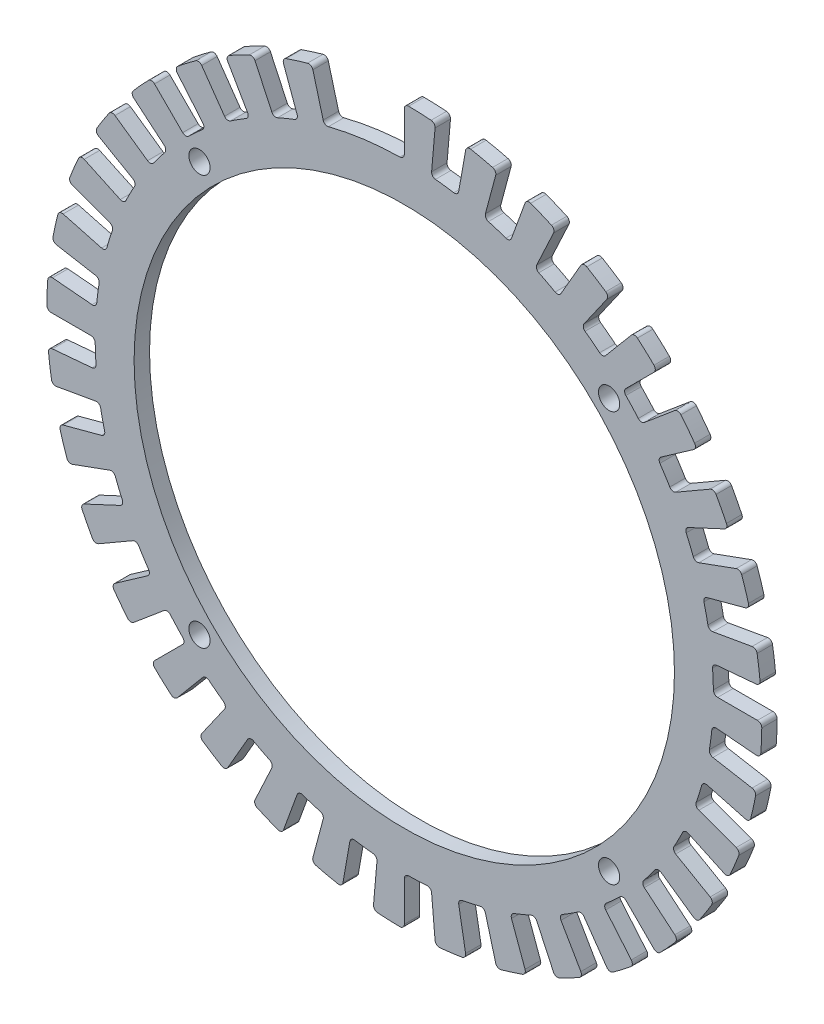
SolidWorks part; units mm, degrees
ref_plane "Front Plane" through (0, 0, 0) normal (0, 0, 1) x (1, 0, 0)
ref_plane "Top Plane" through (0, 0, 0) normal (0, 1, 0) x (1, 0, 0)
ref_plane "Right Plane" through (0, 0, 0) normal (1, 0, 0) x (0, 0, -1)
sketch "Sketch1" plane through (0, 0, 0) normal (0, 0, 1) x (1, 0, 0)
  line L0 (0, 82.7) -> (0, 71.5) construction
  line L1 (7.2078, 82.3853) -> (6.2316, 71.2279) construction
  line L2 (0, 71.5) -> (0, 0) construction
  line L3 (6.2316, 71.2279) -> (0, 0) construction
  line L4 (12.5883, 71.3918) -> (14.186, 80.4528) construction
  line L5 (12.5883, 71.3918) -> (0, 0) construction
  line L8 (0, 0) -> (47.3762, 47.3762) construction
  line L12 (50.5581, 50.5581) -> (47.3762, 47.3762) construction
  line L15 (47.3762, 47.3762) -> (44.1942, 44.1942) construction
  line L18 (7.3144, 72.1301) -> (6.3182, 72.2172) construction
  line L21 (7.3144, 72.1301) -> (7.2135, 71.1352) construction
  line L24 (12.5883, 71.3918) -> (11.6035, 71.5654) construction
  line L27 (11.6035, 71.5654) -> (11.4434, 70.5783) construction
  line L30 (1.0122, 82.6938) -> (1, 81.6939) construction
  line L33 (1, 81.6939) -> (0, 81.6939) construction
  line L36 (7.1201, 81.383) -> (6.1239, 81.4702) construction
  line L39 (6.1239, 81.4702) -> (6.1989, 82.4674) construction
  line L42 (7.1201, 81.383) -> (6.3182, 72.2172)
  line L45 (0, 81.6939) -> (0, 72.4931)
  line L48 (0, 72.4931) -> (-1, 72.4931) construction
  line L51 (-1, 72.4931) -> (-0.9862, 71.4932) construction
  line L109 (0, -82.7) -> (0, -71.5) [skipped]
  line L111 (14.3607, 81.4436) -> (12.4158, 70.4138) [skipped]
  line L115 (41.35, 71.6203) -> (35.75, 61.9208) [skipped]
  line L117 (53.1585, 63.3519) -> (45.9593, 54.7722) [skipped]
  line L118 (-63.3519, -53.1585) -> (-54.7722, -45.9593) [skipped]
  line L119 (63.3519, 53.1585) -> (54.7722, 45.9593) [skipped]
  line L121 (71.6203, 41.35) -> (61.9208, 35.75) [skipped]
  line L123 (77.7126, 28.2851) -> (67.188, 24.4544) [skipped]
  line L125 (81.4436, 14.3607) -> (70.4138, 12.4158) [skipped]
  line L127 (82.7, 0) -> (71.5, 0) [skipped]
  line L129 (81.4436, -14.3607) -> (70.4138, -12.4158) [skipped]
  line L131 (77.7126, -28.2851) -> (67.188, -24.4544) [skipped]
  line L133 (71.6203, -41.35) -> (61.9208, -35.75) [skipped]
  line L135 (63.3519, -53.1585) -> (54.7722, -45.9593) [skipped]
  line L137 (53.1585, -63.3519) -> (45.9593, -54.7722) [skipped]
  line L139 (41.35, -71.6203) -> (35.75, -61.9208) [skipped]
  line L141 (28.2851, -77.7126) -> (24.4544, -67.188) [skipped]
  line L142 (14.3607, -81.4436) -> (12.4158, -70.4138) [skipped]
  line L143 (34.9505, 74.9517) -> (30.2172, 64.801) [skipped]
  line L144 (47.4348, 67.7439) -> (41.0107, 58.5694) [skipped]
  line L145 (58.4777, 58.4777) -> (50.5581, 50.5581) [skipped]
  line L146 (67.7439, 47.4348) -> (58.5694, 41.0107) [skipped]
  line L147 (74.9517, 34.9505) -> (64.801, 30.2172) [skipped]
  line L148 (79.8821, 21.4043) -> (69.0637, 18.5056) [skipped]
  line L149 (82.3853, 7.2078) -> (71.2279, 6.2316) [skipped]
  line L150 (82.3853, -7.2078) -> (71.2279, -6.2316) [skipped]
  line L151 (79.8821, -21.4043) -> (69.0637, -18.5056) [skipped]
  line L152 (74.9517, -34.9505) -> (64.801, -30.2172) [skipped]
  line L153 (67.7439, -47.4348) -> (58.5694, -41.0107) [skipped]
  line L154 (58.4777, -58.4777) -> (50.5581, -50.5581) [skipped]
  line L155 (47.4348, -67.7439) -> (41.0107, -58.5694) [skipped]
  line L156 (34.9505, -74.9517) -> (30.2172, -64.801) [skipped]
  line L157 (21.4043, -79.8821) -> (18.5056, -69.0637) [skipped]
  line L158 (7.2078, -82.3853) -> (6.2316, -71.2279) [skipped]
  line L159 (-7.2078, -82.3853) -> (-6.2316, -71.2279) [skipped]
  line L160 (-21.4043, -79.8821) -> (-18.5056, -69.0637) [skipped]
  line L161 (-34.9505, -74.9517) -> (-30.2172, -64.801) [skipped]
  line L162 (-47.4348, -67.7439) -> (-41.0107, -58.5694) [skipped]
  line L163 (-58.4777, -58.4777) -> (-50.5581, -50.5581) [skipped]
  line L164 (-67.7439, -47.4348) -> (-58.5694, -41.0107) [skipped]
  line L165 (-74.9517, -34.9505) -> (-64.801, -30.2172) [skipped]
  line L166 (-79.8821, -21.4043) -> (-69.0637, -18.5056) [skipped]
  line L167 (-82.3853, -7.2078) -> (-71.2279, -6.2316) [skipped]
  line L168 (-82.3853, 7.2078) -> (-71.2279, 6.2316) [skipped]
  line L169 (-79.8821, 21.4043) -> (-69.0637, 18.5056) [skipped]
  line L170 (-74.9517, 34.9505) -> (-64.801, 30.2172) [skipped]
  line L171 (-67.7439, 47.4348) -> (-58.5694, 41.0107) [skipped]
  line L172 (-58.4777, 58.4777) -> (-50.5581, 50.5581) [skipped]
  line L173 (-47.4348, 67.7439) -> (-41.0107, 58.5694) [skipped]
  line L174 (-34.9505, 74.9517) -> (-30.2172, 64.801) [skipped]
  line L175 (-21.4043, 79.8821) -> (-18.5056, 69.0637) [skipped]
  line L176 (21.4043, 79.8821) -> (18.5056, 69.0637) [skipped]
  line L209 (0, 0) -> (-47.3762, -47.3762) construction
  line L210 (0, 0) -> (-47.3762, 47.3762) construction
  line L211 (0, 0) -> (47.3762, -47.3762) construction
  line L212 (14.186, 80.4528) -> (12.5883, 71.3918)
  line L213 (21.1439, 78.9102) -> (18.7626, 70.023)
  line L214 (27.941, 76.7671) -> (24.7941, 68.1212)
  line L215 (34.5253, 74.0398) -> (30.6369, 65.7011)
  line L216 (40.8469, 70.749) -> (36.2466, 62.7809)
  line L217 (46.8577, 66.9197) -> (41.5803, 59.3829)
  line L218 (52.5118, 62.5811) -> (46.5977, 55.5329)
  line L219 (57.7663, 57.7663) -> (51.2604, 51.2604)
  line L220 (62.5811, 52.5118) -> (55.5329, 46.5977)
  line L221 (66.9197, 46.8577) -> (59.3829, 41.5803)
  line L222 (70.749, 40.8469) -> (62.7809, 36.2466)
  line L223 (74.0398, 34.5253) -> (65.7011, 30.6369)
  line L224 (76.7671, 27.941) -> (68.1212, 24.7941)
  line L225 (78.9102, 21.1439) -> (70.023, 18.7626)
  line L226 (80.4528, 14.186) -> (71.3918, 12.5883)
  line L227 (81.383, 7.1201) -> (72.2172, 6.3182)
  line L228 (81.6939, 0) -> (72.4931, 0)
  line L229 (81.383, -7.1201) -> (72.2172, -6.3182)
  line L230 (80.4528, -14.186) -> (71.3918, -12.5883)
  line L231 (78.9102, -21.1439) -> (70.023, -18.7626)
  line L232 (76.7671, -27.941) -> (68.1212, -24.7941)
  line L233 (74.0398, -34.5253) -> (65.7011, -30.6369)
  line L234 (70.749, -40.8469) -> (62.7809, -36.2466)
  line L235 (66.9197, -46.8577) -> (59.3829, -41.5803)
  line L236 (62.5811, -52.5118) -> (55.5329, -46.5977)
  line L237 (57.7663, -57.7663) -> (51.2604, -51.2604)
  line L238 (52.5118, -62.5811) -> (46.5977, -55.5329)
  line L239 (46.8577, -66.9197) -> (41.5803, -59.3829)
  line L240 (40.8469, -70.749) -> (36.2466, -62.7809)
  line L241 (34.5253, -74.0398) -> (30.6369, -65.7011)
  line L242 (27.941, -76.7671) -> (24.7941, -68.1212)
  line L243 (21.1439, -78.9102) -> (18.7626, -70.023)
  line L244 (14.186, -80.4528) -> (12.5883, -71.3918)
  line L245 (7.1201, -81.383) -> (6.3182, -72.2172)
  line L246 (0, -81.6939) -> (0, -72.4931)
  line L247 (-7.1201, -81.383) -> (-6.3182, -72.2172)
  line L248 (-14.186, -80.4528) -> (-12.5883, -71.3918)
  line L249 (-21.1439, -78.9102) -> (-18.7626, -70.023)
  line L250 (-27.941, -76.7671) -> (-24.7941, -68.1212)
  line L251 (-34.5253, -74.0398) -> (-30.6369, -65.7011)
  line L252 (-40.8469, -70.749) -> (-36.2466, -62.7809)
  line L253 (-46.8577, -66.9197) -> (-41.5803, -59.3829)
  line L254 (-52.5118, -62.5811) -> (-46.5977, -55.5329)
  line L255 (-57.7663, -57.7663) -> (-51.2604, -51.2604)
  line L256 (-62.5811, -52.5118) -> (-55.5329, -46.5977)
  line L257 (-66.9197, -46.8577) -> (-59.3829, -41.5803)
  line L258 (-70.749, -40.8469) -> (-62.7809, -36.2466)
  line L259 (-74.0398, -34.5253) -> (-65.7011, -30.6369)
  line L260 (-76.7671, -27.941) -> (-68.1212, -24.7941)
  line L261 (-78.9102, -21.1439) -> (-70.023, -18.7626)
  line L262 (-80.4528, -14.186) -> (-71.3918, -12.5883)
  line L263 (-81.383, -7.1201) -> (-72.2172, -6.3182)
  line L264 (-81.6939, 0) -> (-72.4931, 0)
  line L265 (-81.383, 7.1201) -> (-72.2172, 6.3182)
  line L266 (-80.4528, 14.186) -> (-71.3918, 12.5883)
  line L267 (-78.9102, 21.1439) -> (-70.023, 18.7626)
  line L268 (-76.7671, 27.941) -> (-68.1212, 24.7941)
  line L269 (-74.0398, 34.5253) -> (-65.7011, 30.6369)
  line L270 (-70.749, 40.8469) -> (-62.7809, 36.2466)
  line L271 (-66.9197, 46.8577) -> (-59.3829, 41.5803)
  line L272 (-62.5811, 52.5118) -> (-55.5329, 46.5977)
  line L273 (-57.7663, 57.7663) -> (-51.2604, 51.2604)
  line L274 (-52.5118, 62.5811) -> (-46.5977, 55.5329)
  line L275 (-46.8577, 66.9197) -> (-41.5803, 59.3829)
  line L276 (-40.8469, 70.749) -> (-36.2466, 62.7809)
  line L277 (-34.5253, 74.0398) -> (-30.6369, 65.7011)
  line L278 (-27.941, 76.7671) -> (-24.7941, 68.1212)
  line L279 (-21.1439, 78.9102) -> (-18.7626, 70.023)
  line L280 (-1.0255, 71.4926) -> (-0.9862, 71.4932)
  circle A0 centre (0, 0) radius 82.7 construction
  circle A1 centre (0, 0) radius 62.5
  circle A73 centre (47.3762, 47.3762) radius 2.4585
  circle A74 centre (47.3762, 47.3762) radius 2.987 construction
  arc A78 (0, 71.5) -> (6.2316, 71.2279) centre (0, 0) cw construction
  arc A79 (6.3182, 72.2172) -> (7.2135, 71.1352) centre (7.3144, 72.1301) ccw
  arc A80 (11.4434, 70.5783) -> (12.5883, 71.3918) centre (11.6035, 71.5654) ccw construction
  arc A81 (7.1201, 81.383) -> (6.1989, 82.4674) centre (6.1239, 81.4702) ccw
  arc A82 (0, 81.6939) -> (1.0122, 82.6938) centre (1, 81.6939) cw
  arc A83 (6.5367, 74.7146) -> (13.0236, 73.8606) centre (0, 0) cw [skipped]
  arc A84 (7.2135, 71.1352) -> (11.4434, 70.5783) centre (0, 0) cw
  arc A85 (0, 82.7) -> (7.2078, 82.3853) centre (0, 0) cw [skipped]
  arc A86 (1.0122, 82.6938) -> (6.1989, 82.4674) centre (0, 0) cw
  arc A87 (28.2851, 77.7126) -> (34.9505, 74.9517) centre (0, 0) cw [skipped]
  arc A88 (31.6964, 67.9731) -> (37.5, 64.9519) centre (0, 0) cw [skipped]
  arc A89 (41.35, 71.6203) -> (47.4348, 67.7439) centre (0, 0) cw [skipped]
  arc A90 (43.0182, 61.4364) -> (48.2091, 57.4533) centre (0, 0) cw [skipped]
  arc A91 (53.1585, 63.3519) -> (58.4777, 58.4777) centre (0, 0) cw [skipped]
  arc A92 (53.033, 53.033) -> (57.4533, 48.2091) centre (0, 0) cw [skipped]
  arc A93 (63.3519, 53.1585) -> (67.7439, 47.4348) centre (0, 0) cw [skipped]
  arc A94 (61.4364, 43.0182) -> (64.9519, 37.5) centre (0, 0) cw [skipped]
  arc A95 (71.6203, 41.35) -> (74.9517, 34.9505) centre (0, 0) cw [skipped]
  arc A96 (67.9731, 31.6964) -> (70.4769, 25.6515) centre (0, 0) cw [skipped]
  arc A97 (77.7126, 28.2851) -> (79.8821, 21.4043) centre (0, 0) cw [skipped]
  arc A98 (72.4444, 19.4114) -> (73.8606, 13.0236) centre (0, 0) cw [skipped]
  arc A99 (81.4436, 14.3607) -> (82.3853, 7.2078) centre (0, 0) cw [skipped]
  arc A100 (74.7146, 6.5367) -> (75, 0) centre (0, 0) cw [skipped]
  arc A101 (82.7, 0) -> (82.3853, -7.2078) centre (0, 0) cw [skipped]
  arc A102 (74.7146, -6.5367) -> (73.8606, -13.0236) centre (0, 0) cw [skipped]
  arc A103 (81.4436, -14.3607) -> (79.8821, -21.4043) centre (0, 0) cw [skipped]
  arc A104 (72.4444, -19.4114) -> (70.4769, -25.6515) centre (0, 0) cw [skipped]
  arc A105 (77.7126, -28.2851) -> (74.9517, -34.9505) centre (0, 0) cw [skipped]
  arc A106 (67.9731, -31.6964) -> (64.9519, -37.5) centre (0, 0) cw [skipped]
  arc A107 (71.6203, -41.35) -> (67.7439, -47.4348) centre (0, 0) cw [skipped]
  arc A108 (61.4364, -43.0182) -> (57.4533, -48.2091) centre (0, 0) cw [skipped]
  arc A109 (63.3519, -53.1585) -> (58.4777, -58.4777) centre (0, 0) cw [skipped]
  arc A110 (53.033, -53.033) -> (48.2091, -57.4533) centre (0, 0) cw [skipped]
  arc A111 (53.1585, -63.3519) -> (47.4348, -67.7439) centre (0, 0) cw [skipped]
  arc A112 (43.0182, -61.4364) -> (37.5, -64.9519) centre (0, 0) cw [skipped]
  arc A113 (41.35, -71.6203) -> (34.9505, -74.9517) centre (0, 0) cw [skipped]
  arc A114 (31.6964, -67.9731) -> (25.6515, -70.4769) centre (0, 0) cw [skipped]
  arc A115 (28.2851, -77.7126) -> (21.4043, -79.8821) centre (0, 0) cw [skipped]
  arc A116 (19.4114, -72.4444) -> (13.0236, -73.8606) centre (0, 0) cw [skipped]
  arc A117 (14.3607, -81.4436) -> (7.2078, -82.3853) centre (0, 0) cw [skipped]
  arc A118 (6.5367, -74.7146) -> (0, -75) centre (0, 0) cw [skipped]
  arc A119 (0, -82.7) -> (-7.2078, -82.3853) centre (0, 0) cw [skipped]
  arc A120 (-6.5367, -74.7146) -> (-13.0236, -73.8606) centre (0, 0) cw [skipped]
  arc A121 (-14.3607, -81.4436) -> (-21.4043, -79.8821) centre (0, 0) cw [skipped]
  arc A122 (-28.2851, -77.7126) -> (-34.9505, -74.9517) centre (0, 0) cw [skipped]
  arc A123 (-19.4114, -72.4444) -> (-25.6515, -70.4769) centre (0, 0) cw [skipped]
  arc A124 (-31.6964, -67.9731) -> (-37.5, -64.9519) centre (0, 0) cw [skipped]
  arc A125 (-41.35, -71.6203) -> (-47.4348, -67.7439) centre (0, 0) cw [skipped]
  arc A126 (-43.0182, -61.4364) -> (-48.2091, -57.4533) centre (0, 0) cw [skipped]
  arc A127 (-53.1585, -63.3519) -> (-58.4777, -58.4777) centre (0, 0) cw [skipped]
  arc A128 (-53.033, -53.033) -> (-57.4533, -48.2091) centre (0, 0) cw [skipped]
  arc A129 (-63.3519, -53.1585) -> (-67.7439, -47.4348) centre (0, 0) cw [skipped]
  arc A130 (-61.4364, -43.0182) -> (-64.9519, -37.5) centre (0, 0) cw [skipped]
  arc A131 (-71.6203, -41.35) -> (-74.9517, -34.9505) centre (0, 0) cw [skipped]
  arc A132 (-67.9731, -31.6964) -> (-70.4769, -25.6515) centre (0, 0) cw [skipped]
  arc A133 (-77.7126, -28.2851) -> (-79.8821, -21.4043) centre (0, 0) cw [skipped]
  arc A134 (-72.4444, -19.4114) -> (-73.8606, -13.0236) centre (0, 0) cw [skipped]
  arc A135 (-81.4436, -14.3607) -> (-82.3853, -7.2078) centre (0, 0) cw [skipped]
  arc A136 (-74.7146, -6.5367) -> (-75, 0) centre (0, 0) cw [skipped]
  arc A137 (-82.7, 0) -> (-82.3853, 7.2078) centre (0, 0) cw [skipped]
  arc A138 (-74.7146, 6.5367) -> (-73.8606, 13.0236) centre (0, 0) cw [skipped]
  arc A139 (-81.4436, 14.3607) -> (-79.8821, 21.4043) centre (0, 0) cw [skipped]
  arc A140 (-72.4444, 19.4114) -> (-70.4769, 25.6515) centre (0, 0) cw [skipped]
  arc A141 (-77.7126, 28.2851) -> (-74.9517, 34.9505) centre (0, 0) cw [skipped]
  arc A142 (-67.9731, 31.6964) -> (-64.9519, 37.5) centre (0, 0) cw [skipped]
  arc A143 (-71.6203, 41.35) -> (-67.7439, 47.4348) centre (0, 0) cw [skipped]
  arc A144 (-61.4364, 43.0182) -> (-57.4533, 48.2091) centre (0, 0) cw [skipped]
  arc A145 (-63.3519, 53.1585) -> (-58.4777, 58.4777) centre (0, 0) cw [skipped]
  arc A146 (-53.033, 53.033) -> (-48.2091, 57.4533) centre (0, 0) cw [skipped]
  arc A147 (-53.1585, 63.3519) -> (-47.4348, 67.7439) centre (0, 0) cw [skipped]
  arc A148 (-43.0182, 61.4364) -> (-37.5, 64.9519) centre (0, 0) cw [skipped]
  arc A149 (-41.35, 71.6203) -> (-34.9505, 74.9517) centre (0, 0) cw [skipped]
  arc A150 (-31.6964, 67.9731) -> (-25.6515, 70.4769) centre (0, 0) cw [skipped]
  arc A151 (-28.2851, 77.7126) -> (-21.4043, 79.8821) centre (0, 0) cw [skipped]
  arc A152 (-19.4114, 72.4444) -> (-13.0236, 73.8606) centre (0, 0) cw [skipped]
  arc A153 (14.3607, 81.4436) -> (21.4043, 79.8821) centre (0, 0) cw [skipped]
  arc A154 (19.4114, 72.4444) -> (25.6515, 70.4769) centre (0, 0) cw [skipped]
  arc A155 (0, 72.4931) -> (-0.9862, 71.4932) centre (-1, 72.4931) cw
  circle A367 centre (-47.3762, -47.3762) radius 2.4585
  circle A368 centre (47.3762, -47.3762) radius 2.4585
  circle A369 centre (-47.3762, 47.3762) radius 2.4585
  circle A370 centre (0, 0) radius 71.5 construction
  arc A371 (12.5883, 71.3918) -> (11.4434, 70.5783) centre (11.6035, 71.5654) cw
  arc A372 (14.186, 80.4528) -> (15.3565, 81.2617) centre (15.1708, 80.2791) cw
  arc A373 (15.3565, 81.2617) -> (20.425, 80.1381) centre (0, 0) cw
  arc A374 (21.1439, 78.9102) -> (20.425, 80.1381) centre (20.178, 79.169) ccw
  arc A375 (18.7626, 70.023) -> (19.4564, 68.8019) centre (19.7285, 69.7641) ccw
  arc A376 (19.4564, 68.8019) -> (23.5254, 67.5189) centre (0, 0) cw
  arc A377 (24.7941, 68.1212) -> (23.5254, 67.5189) centre (23.8544, 68.4633) cw
  arc A378 (27.941, 76.7671) -> (29.2341, 77.3606) centre (28.8806, 76.4251) cw
  arc A379 (29.2341, 77.3606) -> (34.0305, 75.3738) centre (0, 0) cw
  arc A380 (34.5253, 74.0398) -> (34.0305, 75.3738) centre (33.619, 74.4624) ccw
  arc A381 (30.6369, 65.7011) -> (31.1081, 64.3781) centre (31.5432, 65.2784) ccw
  arc A382 (31.1081, 64.3781) -> (34.8925, 62.408) centre (0, 0) cw
  arc A384 (36.2466, 62.7809) -> (34.8925, 62.408) centre (35.3805, 63.2809) cw
  arc A385 (40.8469, 70.749) -> (42.2235, 71.1088) centre (41.713, 70.249) cw
  arc A386 (42.2235, 71.1088) -> (46.602, 68.3194) centre (0, 0) cw
  arc A387 (46.8577, 66.9197) -> (46.602, 68.3194) centre (46.0385, 67.4933) ccw
  arc A388 (41.5803, 59.3829) -> (41.8147, 57.9981) centre (42.3995, 58.8093) ccw
  arc A389 (41.8147, 57.9981) -> (45.1995, 55.4009) centre (0, 0) cw
  arc A390 (46.5977, 55.5329) -> (45.1995, 55.4009) centre (45.8316, 56.1757) cw
  arc A391 (52.5118, 62.5811) -> (53.93, 62.6965) centre (53.2779, 61.9384) cw
  arc A392 (53.93, 62.6965) -> (57.7576, 59.1891) centre (0, 0) cw
  arc A393 (57.7663, 57.7663) -> (57.7576, 59.1891) centre (57.0592, 58.4734) ccw
  arc A394 (51.2604, 51.2604) -> (51.2507, 49.856) centre (51.9675, 50.5533) ccw
  arc A395 (51.2507, 49.856) -> (54.133, 46.7104) centre (0, 0) cw
  arc A396 (55.5329, 46.5977) -> (54.133, 46.7104) centre (54.8902, 47.3637) cw
  arc A397 (62.5811, 52.5118) -> (63.9978, 52.3791) centre (63.2239, 51.7458) cw
  arc A398 (63.9978, 52.3791) -> (67.1582, 48.2604) centre (0, 0) cw
  arc A399 (66.9197, 46.8577) -> (67.1582, 48.2604) centre (66.3461, 47.6768) ccw
  arc A400 (59.3829, 41.5803) -> (59.1295, 40.199) centre (59.9565, 40.7612) ccw
  arc A401 (59.1295, 40.199) -> (61.4218, 36.6007) centre (0, 0) cw
  arc A402 (62.7809, 36.2466) -> (61.4218, 36.6007) centre (62.2809, 37.1126) cw
  arc A403 (70.749, 40.8469) -> (72.1211, 40.4703) centre (71.249, 39.9809) cw
  arc A404 (72.1211, 40.4703) -> (74.5182, 35.8653) centre (0, 0) cw
  arc A405 (74.0398, 34.5253) -> (74.5182, 35.8653) centre (73.6172, 35.4316) ccw
  arc A406 (65.7011, 30.6369) -> (65.2116, 29.3205) centre (66.1237, 29.7306) ccw
  arc A407 (65.2116, 29.3205) -> (66.8443, 25.3788) centre (0, 0) cw
  arc A408 (68.1212, 24.7941) -> (66.8443, 25.3788) centre (67.7792, 25.7338) cw
  arc A409 (76.7671, 27.941) -> (78.053, 27.3318) centre (77.1092, 27.0013) cw
  arc A410 (78.053, 27.3318) -> (79.6141, 22.3805) centre (0, 0) cw
  arc A411 (78.9102, 21.1439) -> (79.6141, 22.3805) centre (78.6514, 22.1099) ccw
  arc A412 (70.023, 18.7626) -> (69.3124, 17.5512) centre (70.2818, 17.7967) ccw
  arc A413 (69.3124, 17.5512) -> (70.2358, 13.3859) centre (0, 0) cw
  arc A414 (71.3918, 12.5883) -> (70.2358, 13.3859) centre (71.2181, 13.5731) cw
  arc A415 (80.4528, 14.186) -> (81.6133, 13.3628) centre (80.6264, 13.2012) cw
  arc A416 (81.6133, 13.3628) -> (82.2909, 8.2156) centre (0, 0) cw
  arc A417 (81.383, 7.1201) -> (82.2909, 8.2156) centre (81.2959, 8.1163) ccw
  arc A418 (72.2172, 6.3182) -> (71.3071, 5.2486) centre (72.3044, 5.322) ccw
  arc A419 (71.3071, 5.2486) -> (71.4932, 0.9862) centre (0, 0) cw
  arc A420 (72.4931, 0) -> (71.4932, 0.9862) centre (72.4931, 1) cw
  arc A421 (81.6939, 0) -> (82.6938, -1.0122) centre (81.6939, -1) cw
  arc A422 (82.6938, -1.0122) -> (82.4674, -6.1989) centre (0, 0) cw
  arc A423 (81.383, -7.1201) -> (82.4674, -6.1989) centre (81.4702, -6.1239) ccw
  arc A424 (72.2172, -6.3182) -> (71.1352, -7.2135) centre (72.1301, -7.3144) ccw
  arc A425 (71.1352, -7.2135) -> (70.5783, -11.4434) centre (0, 0) cw
  arc A426 (71.3918, -12.5883) -> (70.5783, -11.4434) centre (71.5654, -11.6035) cw
  arc A427 (80.4528, -14.186) -> (81.2617, -15.3565) centre (80.2791, -15.1708) cw
  arc A428 (81.2617, -15.3565) -> (80.1381, -20.425) centre (0, 0) cw
  arc A429 (78.9102, -21.1439) -> (80.1381, -20.425) centre (79.169, -20.178) ccw
  arc A430 (70.023, -18.7626) -> (68.8019, -19.4564) centre (69.7641, -19.7285) ccw
  arc A431 (68.8019, -19.4564) -> (67.5189, -23.5254) centre (0, 0) cw
  arc A432 (68.1212, -24.7941) -> (67.5189, -23.5254) centre (68.4633, -23.8544) cw
  arc A433 (76.7671, -27.941) -> (77.3606, -29.2341) centre (76.4251, -28.8806) cw
  arc A434 (77.3606, -29.2341) -> (75.3738, -34.0305) centre (0, 0) cw
  arc A435 (74.0398, -34.5253) -> (75.3738, -34.0305) centre (74.4624, -33.619) ccw
  arc A436 (65.7011, -30.6369) -> (64.3781, -31.1081) centre (65.2784, -31.5432) ccw
  arc A437 (64.3781, -31.1081) -> (62.408, -34.8925) centre (0, 0) cw
  arc A438 (62.7809, -36.2466) -> (62.408, -34.8925) centre (63.2809, -35.3805) cw
  arc A439 (70.749, -40.8469) -> (71.1088, -42.2235) centre (70.249, -41.713) cw
  arc A440 (71.1088, -42.2235) -> (68.3194, -46.602) centre (0, 0) cw
  arc A441 (66.9197, -46.8577) -> (68.3194, -46.602) centre (67.4933, -46.0385) ccw
  arc A442 (59.3829, -41.5803) -> (57.9981, -41.8147) centre (58.8093, -42.3995) ccw
  arc A443 (57.9981, -41.8147) -> (55.4009, -45.1995) centre (0, 0) cw
  arc A444 (55.5329, -46.5977) -> (55.4009, -45.1995) centre (56.1757, -45.8316) cw
  arc A445 (62.5811, -52.5118) -> (62.6965, -53.93) centre (61.9384, -53.2779) cw
  arc A446 (62.6965, -53.93) -> (59.1891, -57.7576) centre (0, 0) cw
  arc A447 (57.7663, -57.7663) -> (59.1891, -57.7576) centre (58.4734, -57.0592) ccw
  arc A448 (51.2604, -51.2604) -> (49.856, -51.2507) centre (50.5533, -51.9675) ccw
  arc A449 (49.856, -51.2507) -> (46.7104, -54.133) centre (0, 0) cw
  arc A450 (46.5977, -55.5329) -> (46.7104, -54.133) centre (47.3637, -54.8902) cw
  arc A451 (52.5118, -62.5811) -> (52.3791, -63.9978) centre (51.7458, -63.2239) cw
  arc A452 (52.3791, -63.9978) -> (48.2604, -67.1582) centre (0, 0) cw
  arc A453 (46.8577, -66.9197) -> (48.2604, -67.1582) centre (47.6768, -66.3461) ccw
  arc A454 (41.5803, -59.3829) -> (40.199, -59.1295) centre (40.7612, -59.9565) ccw
  arc A455 (40.199, -59.1295) -> (36.6007, -61.4218) centre (0, 0) cw
  arc A456 (36.2466, -62.7809) -> (36.6007, -61.4218) centre (37.1126, -62.2809) cw
  arc A457 (40.8469, -70.749) -> (40.4703, -72.1211) centre (39.9809, -71.249) cw
  arc A458 (40.4703, -72.1211) -> (35.8653, -74.5182) centre (0, 0) cw
  arc A459 (34.5253, -74.0398) -> (35.8653, -74.5182) centre (35.4316, -73.6172) ccw
  arc A460 (30.6369, -65.7011) -> (29.3205, -65.2116) centre (29.7306, -66.1237) ccw
  arc A461 (29.3205, -65.2116) -> (25.3788, -66.8443) centre (0, 0) cw
  arc A462 (24.7941, -68.1212) -> (25.3788, -66.8443) centre (25.7338, -67.7792) cw
  arc A463 (27.941, -76.7671) -> (27.3318, -78.053) centre (27.0013, -77.1092) cw
  arc A464 (27.3318, -78.053) -> (22.3805, -79.6141) centre (0, 0) cw
  arc A465 (21.1439, -78.9102) -> (22.3805, -79.6141) centre (22.1099, -78.6514) ccw
  arc A466 (18.7626, -70.023) -> (17.5512, -69.3124) centre (17.7967, -70.2818) ccw
  arc A467 (17.5512, -69.3124) -> (13.3859, -70.2358) centre (0, 0) cw
  arc A468 (12.5883, -71.3918) -> (13.3859, -70.2358) centre (13.5731, -71.2181) cw
  arc A469 (14.186, -80.4528) -> (13.3628, -81.6133) centre (13.2012, -80.6264) cw
  arc A470 (13.3628, -81.6133) -> (8.2156, -82.2909) centre (0, 0) cw
  arc A471 (7.1201, -81.383) -> (8.2156, -82.2909) centre (8.1163, -81.2959) ccw
  arc A472 (6.3182, -72.2172) -> (5.2486, -71.3071) centre (5.322, -72.3044) ccw
  arc A473 (5.2486, -71.3071) -> (0.9862, -71.4932) centre (0, 0) cw
  arc A474 (0, -72.4931) -> (0.9862, -71.4932) centre (1, -72.4931) cw
  arc A475 (0, -81.6939) -> (-1.0122, -82.6938) centre (-1, -81.6939) cw
  arc A476 (-1.0122, -82.6938) -> (-6.1989, -82.4674) centre (0, 0) cw
  arc A477 (-7.1201, -81.383) -> (-6.1989, -82.4674) centre (-6.1239, -81.4702) ccw
  arc A478 (-6.3182, -72.2172) -> (-7.2135, -71.1352) centre (-7.3144, -72.1301) ccw
  arc A479 (-7.2135, -71.1352) -> (-11.4434, -70.5783) centre (0, 0) cw
  arc A480 (-12.5883, -71.3918) -> (-11.4434, -70.5783) centre (-11.6035, -71.5654) cw
  arc A481 (-14.186, -80.4528) -> (-15.3565, -81.2617) centre (-15.1708, -80.2791) cw
  arc A482 (-15.3565, -81.2617) -> (-20.425, -80.1381) centre (0, 0) cw
  arc A483 (-21.1439, -78.9102) -> (-20.425, -80.1381) centre (-20.178, -79.169) ccw
  arc A484 (-18.7626, -70.023) -> (-19.4564, -68.8019) centre (-19.7285, -69.7641) ccw
  arc A485 (-19.4564, -68.8019) -> (-23.5254, -67.5189) centre (0, 0) cw
  arc A486 (-24.7941, -68.1212) -> (-23.5254, -67.5189) centre (-23.8544, -68.4633) cw
  arc A487 (-27.941, -76.7671) -> (-29.2341, -77.3606) centre (-28.8806, -76.4251) cw
  arc A488 (-29.2341, -77.3606) -> (-34.0305, -75.3738) centre (0, 0) cw
  arc A489 (-34.5253, -74.0398) -> (-34.0305, -75.3738) centre (-33.619, -74.4624) ccw
  arc A490 (-30.6369, -65.7011) -> (-31.1081, -64.3781) centre (-31.5432, -65.2784) ccw
  arc A491 (-31.1081, -64.3781) -> (-34.8925, -62.408) centre (0, 0) cw
  arc A492 (-36.2466, -62.7809) -> (-34.8925, -62.408) centre (-35.3805, -63.2809) cw
  arc A493 (-40.8469, -70.749) -> (-42.2235, -71.1088) centre (-41.713, -70.249) cw
  arc A494 (-42.2235, -71.1088) -> (-46.602, -68.3194) centre (0, 0) cw
  arc A495 (-46.8577, -66.9197) -> (-46.602, -68.3194) centre (-46.0385, -67.4933) ccw
  arc A496 (-41.5803, -59.3829) -> (-41.8147, -57.9981) centre (-42.3995, -58.8093) ccw
  arc A497 (-41.8147, -57.9981) -> (-45.1995, -55.4009) centre (0, 0) cw
  arc A498 (-46.5977, -55.5329) -> (-45.1995, -55.4009) centre (-45.8316, -56.1757) cw
  arc A499 (-52.5118, -62.5811) -> (-53.93, -62.6965) centre (-53.2779, -61.9384) cw
  arc A500 (-53.93, -62.6965) -> (-57.7576, -59.1891) centre (0, 0) cw
  arc A501 (-57.7663, -57.7663) -> (-57.7576, -59.1891) centre (-57.0592, -58.4734) ccw
  arc A502 (-51.2604, -51.2604) -> (-51.2507, -49.856) centre (-51.9675, -50.5533) ccw
  arc A503 (-51.2507, -49.856) -> (-54.133, -46.7104) centre (0, 0) cw
  arc A504 (-55.5329, -46.5977) -> (-54.133, -46.7104) centre (-54.8902, -47.3637) cw
  arc A505 (-62.5811, -52.5118) -> (-63.9978, -52.3791) centre (-63.2239, -51.7458) cw
  arc A506 (-63.9978, -52.3791) -> (-67.1582, -48.2604) centre (0, 0) cw
  arc A507 (-66.9197, -46.8577) -> (-67.1582, -48.2604) centre (-66.3461, -47.6768) ccw
  arc A508 (-59.3829, -41.5803) -> (-59.1295, -40.199) centre (-59.9565, -40.7612) ccw
  arc A509 (-59.1295, -40.199) -> (-61.4218, -36.6007) centre (0, 0) cw
  arc A510 (-62.7809, -36.2466) -> (-61.4218, -36.6007) centre (-62.2809, -37.1126) cw
  arc A511 (-70.749, -40.8469) -> (-72.1211, -40.4703) centre (-71.249, -39.9809) cw
  arc A512 (-72.1211, -40.4703) -> (-74.5182, -35.8653) centre (0, 0) cw
  arc A513 (-74.0398, -34.5253) -> (-74.5182, -35.8653) centre (-73.6172, -35.4316) ccw
  arc A514 (-65.7011, -30.6369) -> (-65.2116, -29.3205) centre (-66.1237, -29.7306) ccw
  arc A515 (-65.2116, -29.3205) -> (-66.8443, -25.3788) centre (0, 0) cw
  arc A516 (-68.1212, -24.7941) -> (-66.8443, -25.3788) centre (-67.7792, -25.7338) cw
  arc A517 (-76.7671, -27.941) -> (-78.053, -27.3318) centre (-77.1092, -27.0013) cw
  arc A518 (-78.053, -27.3318) -> (-79.6141, -22.3805) centre (0, 0) cw
  arc A519 (-78.9102, -21.1439) -> (-79.6141, -22.3805) centre (-78.6514, -22.1099) ccw
  arc A520 (-70.023, -18.7626) -> (-69.3124, -17.5512) centre (-70.2818, -17.7967) ccw
  arc A521 (-69.3124, -17.5512) -> (-70.2358, -13.3859) centre (0, 0) cw
  arc A522 (-71.3918, -12.5883) -> (-70.2358, -13.3859) centre (-71.2181, -13.5731) cw
  arc A523 (-80.4528, -14.186) -> (-81.6133, -13.3628) centre (-80.6264, -13.2012) cw
  arc A524 (-81.6133, -13.3628) -> (-82.2909, -8.2156) centre (0, 0) cw
  arc A525 (-81.383, -7.1201) -> (-82.2909, -8.2156) centre (-81.2959, -8.1163) ccw
  arc A526 (-72.2172, -6.3182) -> (-71.3071, -5.2486) centre (-72.3044, -5.322) ccw
  arc A527 (-71.3071, -5.2486) -> (-71.4932, -0.9862) centre (0, 0) cw
  arc A528 (-72.4931, 0) -> (-71.4932, -0.9862) centre (-72.4931, -1) cw
  arc A529 (-81.6939, 0) -> (-82.6938, 1.0122) centre (-81.6939, 1) cw
  arc A530 (-82.6938, 1.0122) -> (-82.4674, 6.1989) centre (0, 0) cw
  arc A531 (-81.383, 7.1201) -> (-82.4674, 6.1989) centre (-81.4702, 6.1239) ccw
  arc A532 (-72.2172, 6.3182) -> (-71.1352, 7.2135) centre (-72.1301, 7.3144) ccw
  arc A533 (-71.1352, 7.2135) -> (-70.5783, 11.4434) centre (0, 0) cw
  arc A534 (-71.3918, 12.5883) -> (-70.5783, 11.4434) centre (-71.5654, 11.6035) cw
  arc A535 (-80.4528, 14.186) -> (-81.2617, 15.3565) centre (-80.2791, 15.1708) cw
  arc A536 (-81.2617, 15.3565) -> (-80.1381, 20.425) centre (0, 0) cw
  arc A537 (-78.9102, 21.1439) -> (-80.1381, 20.425) centre (-79.169, 20.178) ccw
  arc A538 (-70.023, 18.7626) -> (-68.8019, 19.4564) centre (-69.7641, 19.7285) ccw
  arc A539 (-68.8019, 19.4564) -> (-67.5189, 23.5254) centre (0, 0) cw
  arc A540 (-68.1212, 24.7941) -> (-67.5189, 23.5254) centre (-68.4633, 23.8544) cw
  arc A541 (-76.7671, 27.941) -> (-77.3606, 29.2341) centre (-76.4251, 28.8806) cw
  arc A542 (-77.3606, 29.2341) -> (-75.3738, 34.0305) centre (0, 0) cw
  arc A543 (-74.0398, 34.5253) -> (-75.3738, 34.0305) centre (-74.4624, 33.619) ccw
  arc A544 (-65.7011, 30.6369) -> (-64.3781, 31.1081) centre (-65.2784, 31.5432) ccw
  arc A545 (-64.3781, 31.1081) -> (-62.408, 34.8925) centre (0, 0) cw
  arc A546 (-62.7809, 36.2466) -> (-62.408, 34.8925) centre (-63.2809, 35.3805) cw
  arc A547 (-70.749, 40.8469) -> (-71.1088, 42.2235) centre (-70.249, 41.713) cw
  arc A548 (-71.1088, 42.2235) -> (-68.3194, 46.602) centre (0, 0) cw
  arc A549 (-66.9197, 46.8577) -> (-68.3194, 46.602) centre (-67.4933, 46.0385) ccw
  arc A550 (-59.3829, 41.5803) -> (-57.9981, 41.8147) centre (-58.8093, 42.3995) ccw
  arc A551 (-57.9981, 41.8147) -> (-55.4009, 45.1995) centre (0, 0) cw
  arc A552 (-55.5329, 46.5977) -> (-55.4009, 45.1995) centre (-56.1757, 45.8316) cw
  arc A553 (-62.5811, 52.5118) -> (-62.6965, 53.93) centre (-61.9384, 53.2779) cw
  arc A554 (-62.6965, 53.93) -> (-59.1891, 57.7576) centre (0, 0) cw
  arc A555 (-57.7663, 57.7663) -> (-59.1891, 57.7576) centre (-58.4734, 57.0592) ccw
  arc A556 (-51.2604, 51.2604) -> (-49.856, 51.2507) centre (-50.5533, 51.9675) ccw
  arc A557 (-49.856, 51.2507) -> (-46.7104, 54.133) centre (0, 0) cw
  arc A558 (-46.5977, 55.5329) -> (-46.7104, 54.133) centre (-47.3637, 54.8902) cw
  arc A559 (-52.5118, 62.5811) -> (-52.3791, 63.9978) centre (-51.7458, 63.2239) cw
  arc A560 (-52.3791, 63.9978) -> (-48.2604, 67.1582) centre (0, 0) cw
  arc A561 (-46.8577, 66.9197) -> (-48.2604, 67.1582) centre (-47.6768, 66.3461) ccw
  arc A562 (-41.5803, 59.3829) -> (-40.199, 59.1295) centre (-40.7612, 59.9565) ccw
  arc A563 (-40.199, 59.1295) -> (-36.6007, 61.4218) centre (0, 0) cw
  arc A564 (-36.2466, 62.7809) -> (-36.6007, 61.4218) centre (-37.1126, 62.2809) cw
  arc A565 (-40.8469, 70.749) -> (-40.4703, 72.1211) centre (-39.9809, 71.249) cw
  arc A566 (-40.4703, 72.1211) -> (-35.8653, 74.5182) centre (0, 0) cw
  arc A567 (-34.5253, 74.0398) -> (-35.8653, 74.5182) centre (-35.4316, 73.6172) ccw
  arc A568 (-30.6369, 65.7011) -> (-29.3205, 65.2116) centre (-29.7306, 66.1237) ccw
  arc A569 (-29.3205, 65.2116) -> (-25.3788, 66.8443) centre (0, 0) cw
  arc A570 (-24.7941, 68.1212) -> (-25.3788, 66.8443) centre (-25.7338, 67.7792) cw
  arc A571 (-27.941, 76.7671) -> (-27.3318, 78.053) centre (-27.0013, 77.1092) cw
  arc A572 (-27.3318, 78.053) -> (-22.3805, 79.6141) centre (0, 0) cw
  arc A573 (-21.1439, 78.9102) -> (-22.3805, 79.6141) centre (-22.1099, 78.6514) ccw
  arc A574 (-18.7626, 70.023) -> (-17.5512, 69.3124) centre (-17.7967, 70.2818) ccw
  arc A575 (-17.5512, 69.3124) -> (-13.3859, 70.2358) centre (0, 0) cw
  arc A576 (-13.3859, 70.2358) -> (-1.0255, 71.4926) centre (0, 0) cw
  point P29 (0, 0)
  point P252 (0, 0)
  point P728 (0, 0)
  point P763 (0, 0)
  dimension "D2" = 165.4
  dimension "D7" = 4.917
  dimension "D8" = 5.974
  dimension "D12" = 1
  dimension "D14" = 11.2
  dimension "D15" = 11.2
  dimension "D3" = 5
  dimension "D4" = 67
  dimension "D6" = 45
  dimension "D10" = 67
  dimension "D11" = 5
  dimension "D9" = 4.5
  dimension "D5" = 35
  dimension "D13" = 35
extrude "Boss-Extrude1" add sketch "Sketch1" along normal blind 3.5719
